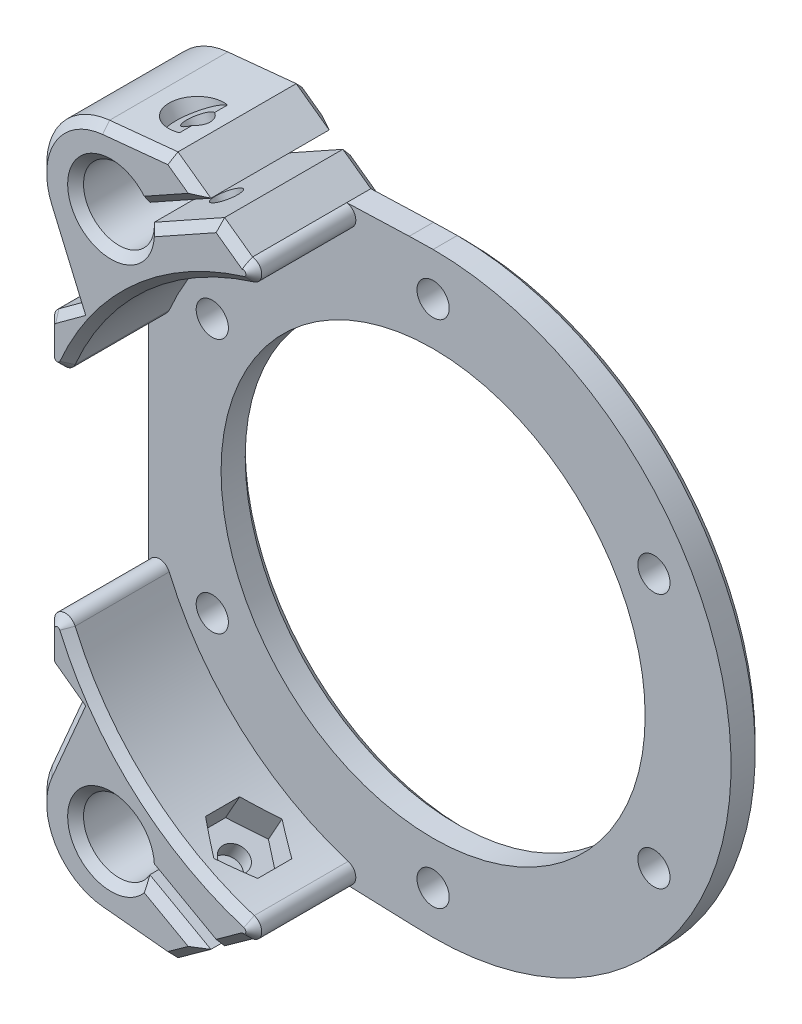
SolidWorks part; units mm, degrees
ref_plane "Front Plane" through (0, 0, 0) normal (0, 0, 1) x (1, 0, 0)
ref_plane "Top Plane" through (0, 0, 0) normal (0, 1, 0) x (1, 0, 0)
ref_plane "Right Plane" through (0, 0, 0) normal (1, 0, 0) x (0, 0, -1)
sketch "Sketch1" plane through (0, 0, 0) normal (0, 0, 1) x (1, 0, 0)
  line L0 (0, 36.75) -> (-10, 33.3337)
  line L1 (-10, 33.3337) -> (-15, 29)
  line L2 (-15, 29) -> (-58.05, 27.5)
  line L3 (-58.05, 27.5) -> (-76.5, 14)
  line L4 (-76.5, 14) -> (-76.5, -14)
  line L5 (-87.0431, 0) -> (20.0163, 0) construction
  line L6 (0, 32.2788) -> (0, 0) construction
  line L7 (76.5, 14) -> (76.5, -14)
  line L8 (58.05, 27.5) -> (76.5, 14)
  line L9 (15, 29) -> (58.05, 27.5)
  line L10 (10, 33.3337) -> (15, 29)
  line L11 (0, 36.75) -> (10, 33.3337)
  line L12 (0, -36.75) -> (10, -33.3337)
  line L13 (10, -33.3337) -> (15, -29)
  line L14 (15, -29) -> (58.05, -27.5)
  line L15 (58.05, -27.5) -> (76.5, -14)
  line L16 (-58.05, -27.5) -> (-76.5, -14)
  line L17 (-15, -29) -> (-58.05, -27.5)
  line L18 (-10, -33.3337) -> (-15, -29)
  line L19 (0, -36.75) -> (-10, -33.3337)
  circle A0 centre (0, 30) radius 3
  circle A1 centre (-50, 0) radius 19.75
  circle A2 centre (50, 0) radius 19.75
  circle A3 centre (0, -30) radius 3
  point P35 (76.5, 0)
  point P36 (-76.5, 0)
  dimension "D1" = 6
  dimension "D2" = 39.5
  dimension "D3" = 60
  dimension "D4" = 100
  dimension "D5" = 153
  dimension "D6" = 73.5
  dimension "D7" = 28
  dimension "D8" = 55
  dimension "D9" = 18.45
  dimension "D10" = 30
  dimension "D11" = 20
  dimension "D12" = 58
extrude "Boss-Extrude1" add sketch "Sketch1" along normal blind 3
sketch "Sketch2" plane through (0, 0, 3) normal (0, 0, 1) x (1, 0, 0)
  line L1 (8.5, 20) -> (-8.5, 20)
  line L2 (12.5, 16) -> (12.5, -16)
  line L3 (8.5, -20) -> (-8.5, -20)
  line L4 (-12.5, 16) -> (-12.5, -16)
  line L5 (12.5, 20) -> (-12.5, -20) construction
  line L6 (12.5, -20) -> (-12.5, 20) construction
  arc A1 (8.5, 20) -> (12.5, 16) centre (8.5, 16) cw
  arc A2 (12.5, -16) -> (8.5, -20) centre (8.5, -16) cw
  arc A3 (-8.5, -20) -> (-12.5, -16) centre (-8.5, -16) cw
  arc A4 (-8.5, 20) -> (-12.5, 16) centre (-8.5, 16) ccw
  point P0 (0, 0)
  dimension "D1" = 4
  dimension "D2" = 25
  dimension "D3" = 40
extrude "Cut-Extrude1" cut sketch "Sketch2" against normal through all
sketch "Sketch3" plane through (0, 0, 3) normal (0, 0, 1) x (1, 0, 0)
  line L0 (-58.05, 27.5) -> (-65, 32.5)
  line L1 (-58.05, 27.5) -> (-76.5, 14) construction
  line L2 (-65, 32.5) -> (-80.2046, 31)
  line L3 (-80.2046, 31) -> (-73.7667, 16)
  line L4 (-73.7667, 16) -> (-58.05, 27.5)
  line L5 (0, 0) -> (0, 46.5274) construction
  line L6 (73.7667, 16) -> (58.05, 27.5)
  line L7 (80.2046, 31) -> (73.7667, 16)
  line L8 (65, 32.5) -> (80.2046, 31)
  line L9 (58.05, 27.5) -> (65, 32.5)
  line L10 (0, 0) -> (-26.0239, 0) construction
  line L11 (58.05, -27.5) -> (65, -32.5)
  line L12 (65, -32.5) -> (80.2046, -31)
  line L13 (80.2046, -31) -> (73.7667, -16)
  line L14 (73.7667, -16) -> (58.05, -27.5)
  line L15 (-73.7667, -16) -> (-58.05, -27.5)
  line L16 (-80.2046, -31) -> (-73.7667, -16)
  line L17 (-65, -32.5) -> (-80.2046, -31)
  line L18 (-58.05, -27.5) -> (-65, -32.5)
  line L19 (-15, 29) -> (-58.05, 27.5) construction
  circle A0 centre (-70.5, 25.5) radius 3.3
  circle A1 centre (70.5, 25.5) radius 3.3
  circle A2 centre (-70.5, -25.5) radius 3.3
  circle A3 centre (70.5, -25.5) radius 3.3
  dimension "D1" = 6.6
  dimension "D2" = 70.5
  dimension "D3" = 25.5
  dimension "D4" = 62
  dimension "D5" = 65
  dimension "D6" = 32
  dimension "D7" = 80.2046
  dimension "D8" = 65
extrude "Boss-Extrude2" add sketch "Sketch3" against normal up to surface (3 mm away) up to face at (0, 0, 0)
fillet "Fillet1" radius 6.5 4 edges at (-80.2046, 31, 1.5) (-80.2046, -31, 1.5) (80.2046, -31, 1.5) (80.2046, 31, 1.5)
sketch "Sketch4" plane through (0, 0, 3) normal (0, 0, 1) x (1, 0, 0)
  line L0 (0, 48.5627) -> (0, -47.8194) construction
  circle A0 centre (-50, 0) radius 23.75 construction
  circle A1 centre (-50, 23.75) radius 1.5
  circle A2 centre (-70.5681, 11.875) radius 1.5
  circle A3 centre (-70.5681, -11.875) radius 1.5
  circle A4 centre (-50, -23.75) radius 1.5
  circle A5 centre (-29.4319, -11.875) radius 1.5
  circle A6 centre (-29.4319, 11.875) radius 1.5
  circle A7 centre (29.4319, 11.875) radius 1.5
  circle A8 centre (29.4319, -11.875) radius 1.5
  circle A9 centre (50, -23.75) radius 1.5
  circle A10 centre (70.5681, -11.875) radius 1.5
  circle A11 centre (70.5681, 11.875) radius 1.5
  circle A12 centre (50, 23.75) radius 1.5
  point P21 (-50, 0)
  point P31 (50, 0)
  dimension "D1" = 47.5
  dimension "D3" = 3
  dimension "D2" = 6
extrude "Cut-Extrude2" cut sketch "Sketch4" against normal through all
sketch "Sketch5" plane through (0, 0, 3) normal (0, 0, 1) x (1, 0, 0)
  line L12 (-57.9916, 27.5812) -> (-50, 27.75)
  line L13 (-76.5591, 14.0807) -> (-76.5, 0)
  line L14 (-76.5, 14) -> (-76.5, -14) construction
  line L15 (-84.5459, 0) -> (89.0041, 0) construction
  line L16 (-73.89, 16.0337) -> (-76.5591, 14.0807)
  line L17 (-76.7941, 22.8002) -> (-73.89, 16.0337)
  line L18 (-64.9722, 32.6032) -> (-71.3771, 31.9714)
  line L19 (-57.9916, 27.5812) -> (-64.9722, 32.6032)
  line L20 (-73.89, 16.0337) -> (-76.5591, 14.0807)
  line L21 (-76.7941, 22.8002) -> (-73.89, 16.0337)
  line L22 (-64.9722, 32.6032) -> (-71.3771, 31.9714)
  line L23 (-57.9916, 27.5812) -> (-64.9722, 32.6032)
  line L24 (-57.9916, -27.5812) -> (-64.9722, -32.6032)
  line L25 (-64.9722, -32.6032) -> (-71.3771, -31.9714)
  line L26 (-76.7941, -22.8002) -> (-73.89, -16.0337)
  line L27 (-73.89, -16.0337) -> (-76.5591, -14.0807)
  line L28 (-76.5591, -14.0807) -> (-76.5, 0)
  line L29 (-57.9916, -27.5812) -> (-50, -27.75)
  line L31 (-98.6251, 56.8967) -> (99.3355, 56.8967)
  line L32 (-98.6251, 56.8967) -> (-98.6251, -48.9335)
  line L33 (-98.6251, -48.9335) -> (99.3355, -48.9335)
  line L34 (99.3355, 56.8967) -> (99.3355, -48.9335)
  arc A0 (-50, -27.75) -> (-50, 27.75) centre (-50, 0) ccw
  arc A4 (-71.3771, -31.9714) -> (-76.7941, -22.8002) centre (-70.7291, -25.4032) cw
  arc A5 (-71.3771, 31.9714) -> (-76.7941, 22.8002) centre (-70.7291, 25.4032) ccw
  arc A6 (-71.3771, 31.9714) -> (-76.7941, 22.8002) centre (-70.7291, 25.4032) ccw
  dimension "D1" = 55.5
  dimension "D2" = 0.1
extrude "Cut-Extrude3" cut sketch "Sketch5" against normal through all
sketch "Sketch6" plane through (0, 0, 3) normal (0, 0, 1) x (1, 0, 0)
  line L0 (-76.7022, 22.8396) -> (-73.7667, 16)
  line L1 (-76.7022, 22.8396) -> (-73.7667, 16) construction
  line L2 (-71.3673, 31.8718) -> (-65, 32.5)
  line L3 (-65, 32.5) -> (-58.05, 27.5)
  line L4 (-58.05, 27.5) -> (-50, 26.75)
  line L5 (-76.5, 14) -> (-73.7667, 16)
  line L6 (-76.5, 14) -> (-76.5, 3.6486)
  line L7 (-76.5, 14) -> (-76.5, -14) construction
  line L8 (-50, 0) -> (-84.0522, 0) construction
  line L9 (-76.5, -14) -> (-76.5, -3.6486)
  line L10 (-76.5, -14) -> (-73.7667, -16)
  line L11 (-58.05, -27.5) -> (-50, -26.75)
  line L12 (-65, -32.5) -> (-58.05, -27.5)
  line L13 (-71.3673, -31.8718) -> (-65, -32.5)
  line L14 (-76.7022, -22.8396) -> (-73.7667, -16)
  arc A0 (-50, 26.75) -> (-76.5, 3.6486) centre (-50, 0) ccw
  arc A1 (-76.7022, 22.8396) -> (-71.3673, 31.8718) centre (-70.7291, 25.4032) cw
  arc A2 (-76.7022, -22.8396) -> (-71.3673, -31.8718) centre (-70.7291, -25.4032) ccw
  arc A3 (-50, -26.75) -> (-76.5, -3.6486) centre (-50, 0) cw
  circle A4 centre (-70.5, 25.5) radius 3.3
  circle A5 centre (-70.5, 25.5) radius 3.3 construction
  circle A6 centre (-70.5, -25.5) radius 3.3
  dimension "D1" = 53.5
extrude "Boss-Extrude3" add sketch "Sketch6" along normal blind 9.5
fillet "Fillet2" radius 1 6 edges at (-50, -26.75, 7.75) (-76.5, -3.6486, 7.75) (-50, 26.75, 7.75) (-76.5, 3.6486, 7.75) (-76.5, -14, 6.25) (-76.5, 14, 6.25)
sketch "Sketch7" plane through (0, 0, 12.5) normal (0, 0, 1) x (1, 0, 0)
  line L0 (-68.7299, 26.5013) -> (-57.4519, 32.7968)
  line L1 (-57.4519, 32.7968) -> (-56.7571, 31.5522)
  line L2 (-56.7571, 31.5522) -> (-67.9885, 25.2827)
  line L3 (-67.9885, 25.2827) -> (-68.7299, 26.5013)
  line L4 (-70.5, 25.5) -> (-59.611, 31.5783) construction
  line L5 (-50, 0) -> (-95.3725, 0) construction
  line L6 (-70.5, -25.5) -> (-59.611, -31.5783) construction
  line L7 (-67.9885, -25.2827) -> (-68.7299, -26.5013)
  line L8 (-56.7571, -31.5522) -> (-67.9885, -25.2827)
  line L9 (-57.4519, -32.7968) -> (-56.7571, -31.5522)
  line L10 (-68.7299, -26.5013) -> (-57.4519, -32.7968)
extrude "Cut-Extrude4" cut sketch "Sketch7" against normal through all
sketch "Sketch8" plane through (-26.9121, 48.2118, 0) normal (-0.4874, 0.8732, 0) x (0.8732, 0.4874, 0)
  line L0 (-25.9438, -3) -> (-25.9438, -12.5) construction
  line L1 (-57.1843, -3) -> (-15.9087, -3) construction
  line L2 (-36.8959, -12.5) -> (-21.1915, -12.5) construction
  circle A0 centre (-43.0415, -7.75) radius 1.2
  point P11 (-25.9438, -7.75)
  dimension "D1" = 2.4
extrude "Cut-Extrude5" cut sketch "Sketch8" against normal blind 18 from offset 10
sketch "Sketch9" plane through (-26.9121, 48.2118, 0) normal (-0.4874, 0.8732, 0) x (0.8732, 0.4874, 0)
  circle A0 centre (-43.0415, -7.75) radius 2.325
  dimension "D1" = 4.65
extrude "Cut-Extrude6" cut sketch "Sketch9" against normal blind 4.5 from offset 10
sketch "Sketch10" plane through (-26.9121, 48.2118, 0) normal (-0.4874, 0.8732, 0) x (0.8732, 0.4874, 0)
  line L1 (-43.0415, -4.5746) -> (-45.7915, -6.1623)
  line L2 (-45.7915, -6.1623) -> (-45.7915, -9.3377)
  line L3 (-45.7915, -9.3377) -> (-43.0415, -10.9254)
  line L4 (-43.0415, -10.9254) -> (-40.2915, -9.3377)
  line L5 (-40.2915, -9.3377) -> (-40.2915, -6.1623)
  line L6 (-40.2915, -6.1623) -> (-43.0415, -4.5746)
  circle A0 centre (-43.0415, -7.75) radius 2.75 construction
  dimension "D1" = 5.5
extrude "Cut-Extrude7" cut sketch "Sketch10" along normal blind 3.5 from offset 5 offset against normal yes
mirror "Mirror1" about plane through (0, 0, 0) normal (0, 1, 0) of "Cut-Extrude7", "Cut-Extrude6", "Cut-Extrude5"
chamfer "Chamfer1" distance 0.75 angle 45 33 edges at (-27.9319, 11.875, 0) (-27.9319, -11.875, 0) (-48.5, -23.75, 0) (-69.0681, -11.875, 0) (-69.0681, 11.875, 0) (-48.5, 23.75, 0) (-30.25, 0, 0) (-63.4672, 31.3973, 0) (-68.1836, 32.1859, 0) (-76.3257, 28.7089, 0) (-75.2344, 19.4198, 0) (-74.9286, 15.1498, 0) (-76.3918, 13.9451, 0) (-76.5, 0, 0) (-76.3918, -13.9451, 0) (-74.9286, -15.1498, 0) (-75.2344, -19.4198, 0) (-76.3257, -28.7089, 0) (-68.1836, -32.1859, 0) (-63.4672, -31.3973, 0) (-64.7793, -28.7066, 0) (-73.6627, -24.558, 0) (-63.932, -27.5471, 0) (-59.3534, -28.4377, 0) (-55.1362, -27.6015, 0) (-51.1112, -27.7265, 0) (-22.25, 0, 0) (-51.1112, 27.7265, 0) (-55.1362, 27.6015, 0) (-59.3534, 28.4377, 0) (-63.932, 27.5471, 0) (-73.6627, 24.558, 0) (-64.7793, 28.7066, 0)
chamfer "Chamfer2" distance 0.74 angle 45 28 edges at (-63.4672, -31.3973, 12.5) (-64.7793, -28.7066, 12.5) (-59.3534, -28.4377, 12.5) (-63.932, -27.5471, 12.5) (-73.6627, -24.558, 12.5) (-68.1836, -32.1859, 12.5) (-57.2017, -26.5863, 12.5) (-76.3257, -28.7089, 12.5) (-75.2344, -19.4198, 12.5) (-74.9286, -15.1498, 12.5) (-76.3918, -13.9451, 12.5) (-76.5, -12.2192, 12.5) (-75.7013, -9.9664, 12.5) (-67.8912, -19.8864, 12.5) (-74.9286, 15.1498, 12.5) (-76.3918, 13.9451, 12.5) (-75.2344, 19.4198, 12.5) (-76.5, 12.2192, 12.5) (-76.3257, 28.7089, 12.5) (-75.7013, 9.9664, 12.5) (-68.1836, 32.1859, 12.5) (-63.4672, 31.3973, 12.5) (-64.7793, 28.7066, 12.5) (-73.6627, 24.558, 12.5) (-63.932, 27.5471, 12.5) (-59.3534, 28.4377, 12.5) (-57.2017, 26.5863, 12.5) (-67.8912, 19.8864, 12.5)
